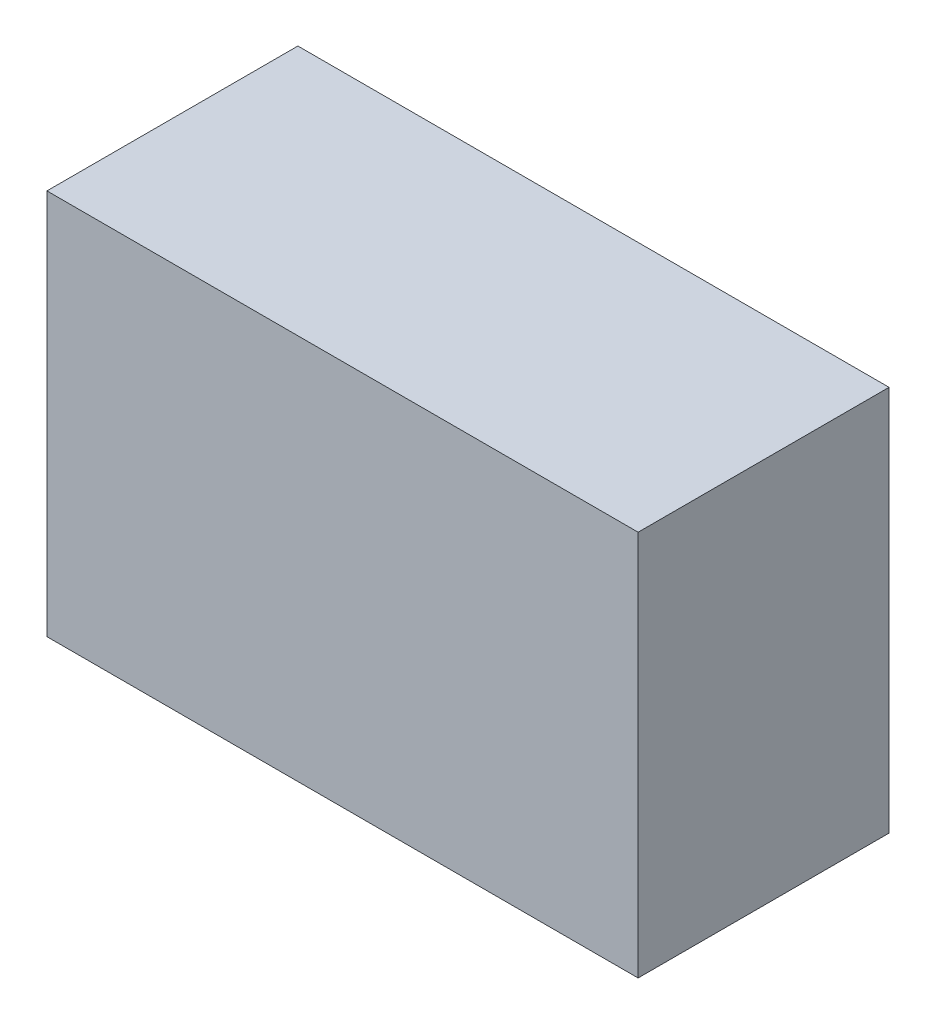
SolidWorks part; units mm, degrees
ref_plane "Front" through (0, 0, 0) normal (0, 0, 1) x (1, 0, 0)
ref_plane "Top" through (0, 0, 0) normal (0, 1, 0) x (1, 0, 0)
ref_plane "Right" through (0, 0, 0) normal (1, 0, 0) x (0, 0, -1)
sketch "Sketch2" plane through (0, 0, 0) normal (0, 1, 0) x (1, 0, 0)
  line L0 (-77.7875, 0) -> (77.7875, 0) construction
  line L1 (-77.7875, 33.02) -> (77.7875, 33.02)
  line L2 (-77.7875, 33.02) -> (-77.7875, -33.02)
  line L3 (-77.7875, -33.02) -> (77.7875, -33.02)
  line L4 (77.7875, 33.02) -> (77.7875, -33.02)
  dimension "D1" = 155.575
  dimension "D2" = 66.04
extrude "Extrude1" add sketch "Sketch2" along normal blind 101.6
